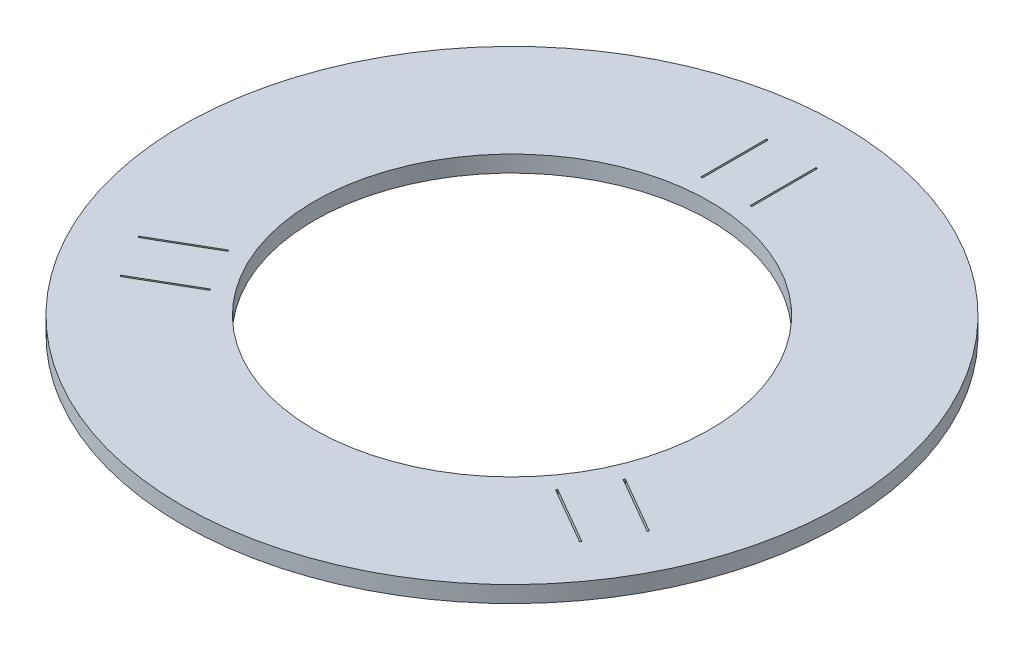
SolidWorks part; units mm, degrees
ref_plane "Front Plane" through (0, 0, 0) normal (0, 0, 1) x (1, 0, 0)
ref_plane "Top Plane" through (0, 0, 0) normal (0, 1, 0) x (1, 0, 0)
ref_plane "Right Plane" through (0, 0, 0) normal (1, 0, 0) x (0, 0, -1)
sketch "Sketch2" plane through (0, 0, 0) normal (0, 1, 0) x (1, 0, 0)
  circle A0 centre (0, 0) radius 100
  dimension "D1" = 200
extrude "Boss-Extrude1" add sketch "Sketch2" along normal blind 5
sketch "Sketch3" plane through (0, 5, 0) normal (0, 1, 0) x (1, 0, 0)
  line L0 (0, 0) -> (0, 100) construction
  line L1 (-7.5, 75) -> (7.5, 75) construction
  line L3 (-7.75, 65) -> (-7.25, 65)
  line L4 (-7.75, 65) -> (-7.75, 85)
  line L5 (-7.75, 85) -> (-7.25, 85)
  line L6 (-7.25, 65) -> (-7.25, 85)
  line L7 (-7.75, 65) -> (-7.25, 85) construction
  line L8 (-7.75, 85) -> (-7.25, 65) construction
  line L9 (7.25, 65) -> (7.75, 65)
  line L10 (7.25, 65) -> (7.25, 85)
  line L11 (7.25, 85) -> (7.75, 85)
  line L12 (7.75, 65) -> (7.75, 85)
  line L13 (7.25, 65) -> (7.75, 85) construction
  line L14 (7.25, 85) -> (7.75, 65) construction
  line L30 (60.1667, -25.7883) -> (77.4872, -35.7883)
  line L31 (60.1667, -25.7883) -> (59.9167, -26.2213)
  line L32 (59.9167, -26.2213) -> (77.2372, -36.2213)
  line L33 (77.4872, -35.7883) -> (77.2372, -36.2213)
  line L34 (52.6667, -38.7787) -> (69.9872, -48.7787)
  line L35 (52.6667, -38.7787) -> (52.4167, -39.2117)
  line L36 (52.4167, -39.2117) -> (69.7372, -49.2117)
  line L37 (69.9872, -48.7787) -> (69.7372, -49.2117)
  line L38 (-52.4167, -39.2117) -> (-69.7372, -49.2117)
  line L39 (-52.4167, -39.2117) -> (-52.6667, -38.7787)
  line L40 (-52.6667, -38.7787) -> (-69.9872, -48.7787)
  line L41 (-69.7372, -49.2117) -> (-69.9872, -48.7787)
  line L42 (-59.9167, -26.2213) -> (-77.2372, -36.2213)
  line L43 (-59.9167, -26.2213) -> (-60.1667, -25.7883)
  line L44 (-60.1667, -25.7883) -> (-77.4872, -35.7883)
  line L45 (-77.2372, -36.2213) -> (-77.4872, -35.7883)
  circle A0 centre (0, 0) radius 100 construction
  point P8 (0, 75)
  point P17 (0, 0)
  point P36 (0, 0)
  point P37 (0, 0)
  dimension "D1" = 15
  dimension "D2" = 20
  dimension "D3" = 0.5
  dimension "D4" = 75
  dimension "D5" = 3
extrude "Cut-Extrude1" cut sketch "Sketch3" against normal through all
sketch "Sketch4" plane through (0, 5, 0) normal (0, 1, 0) x (1, 0, 0)
  circle A0 centre (0, 0) radius 60
  dimension "D1" = 120
extrude "Cut-Extrude2" cut sketch "Sketch4" against normal through all
equation "\"Leg_Spacing\"=15"
equation "\"D1@Sketch3\"=\"Leg_Spacing\""
equation "\"Leaf_Spring_Slot_Width\"=20"
equation "\"D2@Sketch3\"=\"Leaf_Spring_Slot_Width\""
equation "\"Leaf_Spring_Thickness\"=0.5"
equation "\"D3@Sketch3\"=\"Leaf_Spring_Thickness\""
equation "\"Inner_Radius\"=75"
equation "\"D4@Sketch3\"=\"Inner_Radius\""
equation "\"Camera\"=120"
equation "\"D1@Sketch4\"=\"Camera\""
